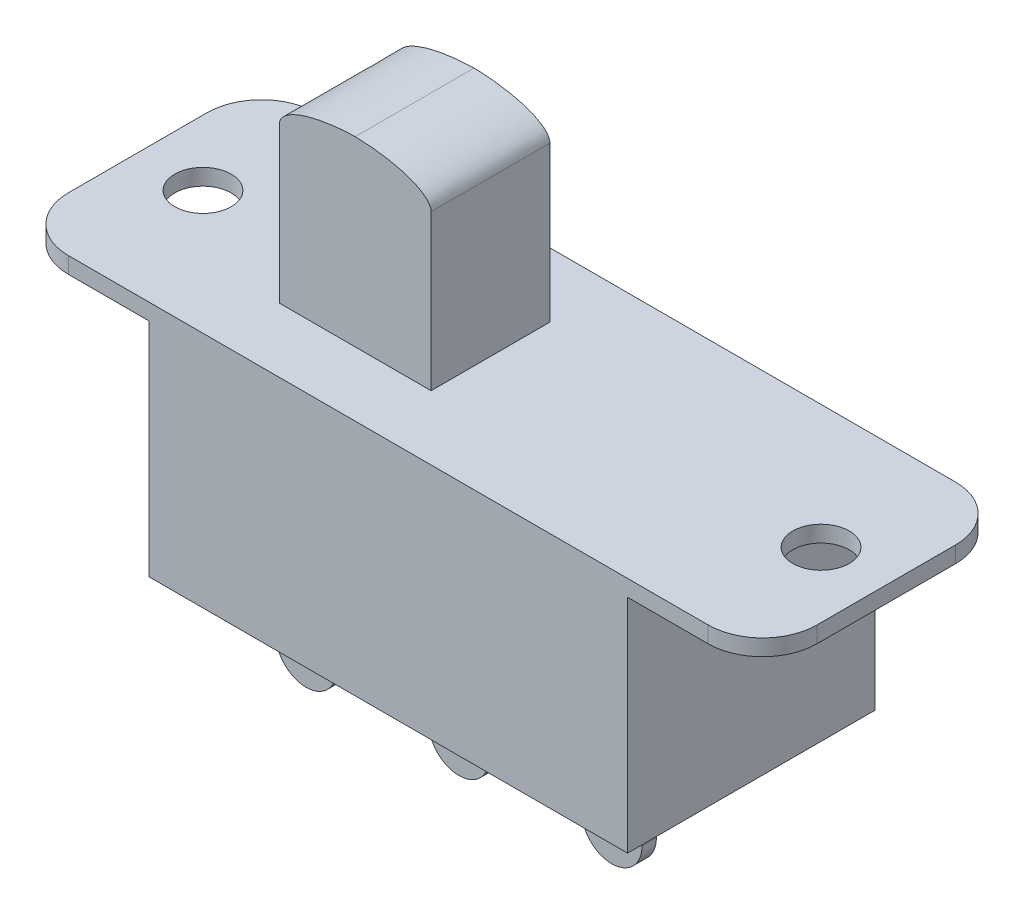
SolidWorks part; units mm, degrees
ref_plane "Front" through (0, 0, 0) normal (0, 0, 1) x (1, 0, 0)
ref_plane "Top" through (0, 0, 0) normal (0, 1, 0) x (1, 0, 0)
ref_plane "Right" through (0, 0, 0) normal (1, 0, 0) x (0, 0, -1)
sketch "Sketch1" plane through (0, 0, 0) normal (0, 1, 0) x (1, 0, 0)
  line L1 (2.54, 0) -> (32.4231, 0)
  line L2 (0, 2.54) -> (0, 9.017)
  line L3 (2.54, 11.557) -> (32.4231, 11.557)
  line L4 (34.9631, 2.54) -> (34.9631, 9.017)
  arc A0 (32.4231, 11.557) -> (34.9631, 9.017) centre (32.4231, 9.017) cw
  arc A1 (32.4231, 0) -> (34.9631, 2.54) centre (32.4231, 2.54) ccw
  arc A2 (2.54, 0) -> (0, 2.54) centre (2.54, 2.54) cw
  arc A3 (0, 9.017) -> (2.54, 11.557) centre (2.54, 9.017) cw
  point P7 (34.9631, 11.557)
  point P12 (0, 0)
  point P15 (0, 11.557)
  dimension "D3" = 2.54
  dimension "D1" = 34.9631
  dimension "D2" = 11.557
extrude "Boss-Extrude1" add sketch "Sketch1" against normal blind 0.762
sketch "Sketch2" plane through (0, 0, 0) normal (0, 1, 0) x (1, 0, 0)
  line L0 (2.54, 0) -> (32.4231, 0) construction
  line L1 (6.3056, 0) -> (28.6576, 0)
  line L2 (6.3056, 0) -> (6.3056, 11.557)
  line L3 (6.3056, 11.557) -> (28.6576, 11.557)
  line L4 (28.6576, 0) -> (28.6576, 11.557)
  line L5 (32.4231, 11.557) -> (2.54, 11.557) construction
  point P8 (17.4816, 11.557)
  dimension "D1" = 22.352
extrude "Boss-Extrude2" add sketch "Sketch2" against normal blind 11.1125
sketch "Sketch3" plane through (0, 0, 0) normal (0, 1, 0) x (1, 0, 0)
  line L1 (9.3912, 8.5534) -> (16.4778, 8.5534)
  line L2 (9.3912, 8.5534) -> (9.3912, 3.0035)
  line L3 (9.3912, 3.0035) -> (16.4778, 3.0035)
  line L4 (16.4778, 8.5534) -> (16.4778, 3.0035)
  line L5 (0, 9.017) -> (0, 2.54) construction
  point P4 (9.3912, 5.7785)
  point P7 (0, 5.7785)
  dimension "D1" = 7.0866
  dimension "D2" = 5.5499
extrude "Boss-Extrude3" add sketch "Sketch3" along normal blind 8.509
fillet "Fillet4" radius 1.27 2 edges at (16.4778, 8.509, -5.7785) (9.3912, 8.509, -5.7785) second distance 3.81 first distance on face at (16.4778, 4.2545, -5.7785) first distance on face at (9.3912, 4.2545, -5.7785)
sketch "Sketch4" plane through (0, 0, 0) normal (0, 1, 0) x (1, 0, 0)
  line L0 (0, 9.017) -> (0, 2.54) construction
  line L1 (34.9631, 2.54) -> (34.9631, 9.017) construction
  circle A0 centre (3.048, 5.7785) radius 1.319
  circle A1 centre (31.9151, 5.7785) radius 1.319
  point P6 (0, 5.7785)
  dimension "D1" = 3.048
  dimension "D2" = 3.048
extrude "Cut-Extrude1" cut sketch "Sketch4" against normal through all
sketch "Sketch5" plane through (0, -11.1125, 0) normal (0, -1, 0) x (1, 0, 0)
  line L0 (6.3056, 0) -> (28.6576, 0) construction
  line L1 (8.9345, -3.302) -> (11.7539, -3.302)
  line L2 (8.9345, -3.302) -> (8.9345, -3.9751)
  line L3 (8.9345, -3.9751) -> (11.7539, -3.9751)
  line L4 (11.7539, -3.302) -> (11.7539, -3.9751)
  line L5 (16.0719, -3.302) -> (18.8913, -3.302)
  line L6 (16.0719, -3.302) -> (16.0719, -3.9751)
  line L7 (16.0719, -3.9751) -> (18.8913, -3.9751)
  line L8 (18.8913, -3.302) -> (18.8913, -3.9751)
  line L9 (23.2093, -3.302) -> (26.0287, -3.302)
  line L10 (23.2093, -3.302) -> (23.2093, -3.9751)
  line L11 (23.2093, -3.9751) -> (26.0287, -3.9751)
  line L12 (26.0287, -3.302) -> (26.0287, -3.9751)
  point P14 (17.4816, 0)
  point P15 (17.4816, -3.302)
  dimension "D1" = 2.8194
  dimension "D2" = 0.6731
  dimension "D3" = 3.302
  dimension "D4" = 4.318
  dimension "D5" = 4.318
extrude "Boss-Extrude4" add sketch "Sketch5" along normal blind 4.1021
fillet "Fillet5" 2 edges at (8.9345, -15.2146, -3.6385) (11.7539, -15.2146, -3.6385) type full round first side face at (8.9345, -13.1635, -3.6385) second side face at (11.7539, -13.1635, -3.6385) middle face at (10.3442, -15.2146, -3.6385)
fillet "Fillet6" 2 edges at (16.0719, -15.2146, -3.6385) (18.8913, -15.2146, -3.6385) type full round first side face at (16.0719, -13.1635, -3.6385) second side face at (18.8913, -13.1635, -3.6385) middle face at (17.4816, -15.2146, -3.6385)
fillet "Fillet7" 2 edges at (23.2093, -15.2146, -3.6385) (26.0287, -15.2146, -3.6385) type full round first side face at (23.2093, -13.1635, -3.6385) second side face at (26.0287, -13.1635, -3.6385) middle face at (24.619, -15.2146, -3.6385)
